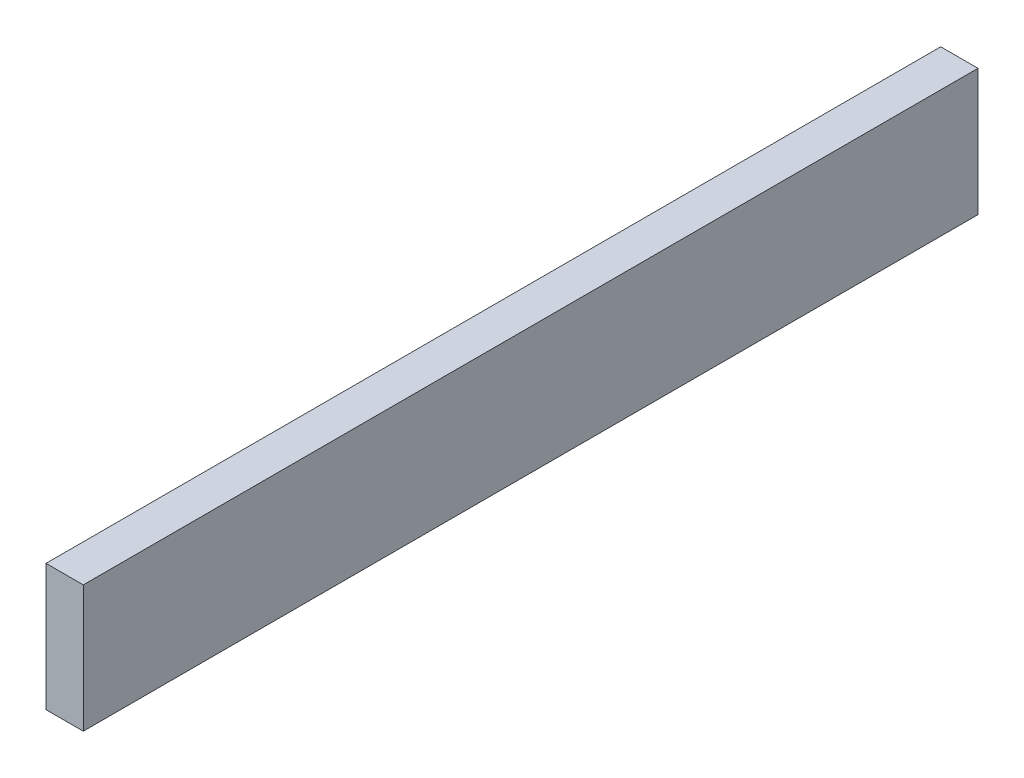
SolidWorks part; units mm, degrees
ref_plane "Front" through (0, 0, 0) normal (0, 0, 1) x (1, 0, 0)
ref_plane "Top" through (0, 0, 0) normal (0, 1, 0) x (1, 0, 0)
ref_plane "Right" through (0, 0, 0) normal (1, 0, 0) x (0, 0, -1)
sketch "Skizze1" plane through (0, 0, 0) normal (1, 0, 0) x (0, 0, -1)
  line L1 (0, 0) -> (120, 0)
  line L2 (0, 0) -> (0, 17)
  line L3 (0, 17) -> (120, 17)
  line L4 (120, 0) -> (120, 17)
  dimension "D1" = 17
  dimension "D2" = 120
extrude "Aufsatz-Linear austragen1" add sketch "Skizze1" along normal blind 5
